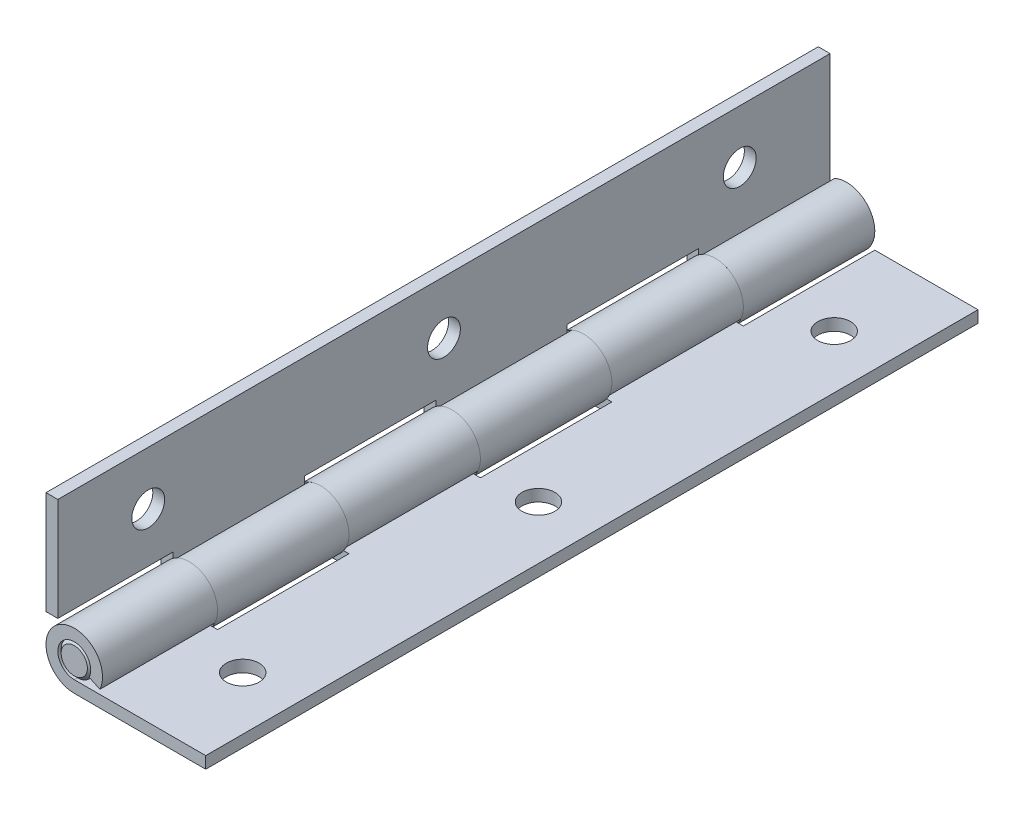
SolidWorks part; units mm, degrees
note: '?' marks a value the reader was unsure of.
material "6061-T6 (SS)"
ref_plane "Front Plane" through (0, 0, 0) normal (0, 0, 1) x (1, 0, 0)
ref_plane "Top Plane" through (0, 0, 0) normal (0, 1, 0) x (1, 0, 0)
ref_plane "Right Plane" through (0, 0, 0) normal (1, 0, 0) x (0, 0, -1)
sketch "Sketch1" plane through (0, 0, 0) normal (0, 0, 1) x (1, 0, 0)
  line L0 (4.4432, -3.175) -> (25.4, -3.175)
  line L1 (25.4, -3.175) -> (25.4, -5.461)
  line L2 (25.4, -5.461) -> (0, -5.461)
  line L3 (0, 0) -> (0, 3.175) construction
  line L4 (-3.175, 0) -> (-5.461, 0) construction
  line L5 (2.8775, -1.3418) -> (4.9493, -2.3079) construction
  line L6 (-2.8775, -1.3418) -> (-4.9493, -2.3079) construction
  circle A0 centre (0, 0) radius 3.175
  circle A1 centre (0, 0) radius 5.461
  dimension "knuckle dia" = 10.922
  dimension "leaf thickness" = 2.286
  dimension "open width" = 50.8
  dimension "D5" = 25
  dimension "D6" = 25
sketch "Sketch2" plane through (0, 0, 0) normal (0, 0, 1) x (1, 0, 0)
  line L0 (25.4, -3.175) -> (25.4, -5.461) construction
  line L1 (4.4432, -3.175) -> (25.4, -3.175) construction
  line L2 (2.8775, -1.3418) -> (4.9493, -2.3079) construction
  line L3 (25.4, -5.461) -> (0, -5.461) construction
  line L4 (25.4, -3.175) -> (25.4, -5.461)
  line L5 (0, -3.175) -> (25.4, -3.175)
  line L6 (2.8775, -1.3418) -> (4.9493, -2.3079)
  line L7 (25.4, -5.461) -> (0, -5.461)
  circle A0 centre (0, 0) radius 3.175 construction
  circle A1 centre (0, 0) radius 5.461 construction
  arc A2 (2.8775, -1.3418) -> (0, -3.175) centre (0, 0) ccw
  arc A3 (4.9493, -2.3079) -> (0, -5.461) centre (0, 0) ccw
extrude "Extrude1" add sketch "Sketch2" along normal mid plane 149.225
sketch "Sketch3" plane through (0, -3.175, 0) normal (0, 1, 0) x (1, 0, 0)
  line L1 (-5.461, 74.6125) -> (5.461, 74.6125)
  line L2 (-5.461, 74.6125) -> (-5.461, 49.2125)
  line L3 (-5.461, 49.2125) -> (5.461, 49.2125)
  line L4 (5.461, 74.6125) -> (5.461, 49.2125)
  line L6 (5.461, 74.6125) -> (-5.461, 74.6125) construction
  line L7 (5.461, -74.6125) -> (5.461, 74.6125) construction
  line L8 (-5.461, 74.6125) -> (-5.461, -74.6125) construction
  dimension "knuckle length" = 25.4
extrude "Cut-Extrude1" cut sketch "Sketch3" against normal mid plane 50.8
pattern_linear "LPattern1" count 3 spacing 50.8 along (0, 0, 1) of "Cut-Extrude1"
sketch "Sketch5" plane through (0, 0, -74.6125) normal (0, 0, -1) x (-1, 0, 0)
  line L0 (-4.4432, -3.175) -> (-25.4, -3.175) construction
  line L1 (-25.4, -5.461) -> (0, -5.461) construction
  line L2 (0, -3.175) -> (25.4, -3.175)
  line L3 (25.4, -5.461) -> (0, -5.461)
  line L4 (2.8775, -1.3418) -> (4.9493, -2.3079) construction
  line L5 (2.8775, -1.3418) -> (4.9493, -2.3079)
  line L6 (25.4, -3.175) -> (25.4, -5.461)
  line L8 (0, 0) -> (0, -5.461) construction
  circle A0 centre (0, 0) radius 5.461 construction
  arc A1 (4.9493, -2.3079) -> (0, -5.461) centre (0, 0) ccw
  circle A2 centre (0, 0) radius 3.175 construction
  arc A3 (2.8775, -1.3418) -> (0, -3.175) centre (0, 0) ccw
  dimension "D1" = 50.8
extrude "Extrude2" add sketch "Sketch5" against normal blind 25.4 separate body
pattern_linear "LPattern3" count 3 spacing 50.8 along (0, 0, 1) of bodies 104
sketch "Sketch6" plane through (0, 0, -74.6125) normal (0, 0, -1) x (-1, 0, 0)
  line L0 (0, -5.461) -> (25.4, -5.461) construction
  line L1 (25.4, -3.175) -> (5.4864, -3.175)
  line L2 (25.4, -3.175) -> (25.4, -5.461)
  line L3 (25.4, -5.461) -> (5.4864, -5.461)
  line L4 (5.4864, -3.175) -> (5.4864, -5.461)
  line L6 (25.4, -3.175) -> (0, -3.175) construction
  line L7 (5.461, 1.5054) -> (5.461, -2.5761) construction
  arc A0 (4.9493, -2.3079) -> (0, -5.461) centre (0, 0) ccw construction
  dimension "D1" = 0.0254
extrude "Extrude5" add sketch "Sketch6" against normal blind 149.225
sketch "Sketch7" plane through (0, 0, 0) normal (0, 0, 1) x (1, 0, 0)
  circle A0 centre (0, 0) radius 3.175 construction
  circle A1 centre (0, 0) radius 3.175
extrude "Extrude4" add sketch "Sketch7" along normal mid plane 149.225 separate body
chamfer "Chamfer1" distance 0.635 angle 45 2 edges at (3.175, 0, 74.6125) (3.175, 0, -74.6125)
sketch "Sketch8" plane through (0, 0, 0) normal (0, 1, 0) x (1, 0, 0)
  line L0 (25.4, 0) -> (-25.4, 0) construction
  line L1 (25.4, 0) -> (0, 0) construction
  line L2 (-25.4, -74.6125) -> (-25.4, 74.6125) construction
  line L3 (25.4, -74.6125) -> (25.4, 74.6125) construction
ref_axis "Axis1" through (-25.4, 0, 0) along (1, 0, 0)?
ref_plane "  " through (0, 0, 0) normal (0, 0.866, 0.5) x (1, 0, 0)
sketch "Sketch9" plane through (0, 0, 0) normal (0, 1, 0) x (1, 0, 0)
  line L0 (5.461, 49.2125) -> (5.461, 74.6125) construction
  point P0 (-25.4, 74.6125)
  point P1 (25.4, 74.6125)
  point P3 (-25.4, -74.6125)
  point P5 (25.4, -74.6125)
  point P7 (5.461, 49.2125)
sketch "Sketch11" plane through (0, 0, 0) normal (0, 0, 1) x (1, 0, 0)
  line L0 (-5.461, 0) -> (-5.461, -5.461)
  line L1 (-5.461, -5.461) -> (5.461, -5.461)
  line L2 (5.461, -5.461) -> (5.461, 0)
  line L3 (0, -5.461) -> (25.4, -5.461) construction
  circle A0 centre (0, 0) radius 5.461
  circle A1 centre (0, 0) radius 5.461 construction
sketch "Sketch12" plane through (0, -3.175, 0) normal (0, 1, 0) x (1, 0, 0)
  line L0 (31.5242, 0) -> (-103.7671, 0) construction
  line L1 (0, -45.7265) -> (0, 82.3405) construction
  circle A0 centre (-15.0812, 57.15) radius 3.175
  circle A1 centre (-15.0812, 0) radius 3.175
  circle A2 centre (-15.0812, -57.15) radius 3.175
  circle A3 centre (15.0812, 0) radius 3.175
  circle A4 centre (15.0812, 57.15) radius 3.175
  circle A5 centre (15.0812, -57.15) radius 3.175
  dimension "D2" = 6.35
  dimension "D1" = 30.1625
  dimension "D3" = 57.15
extrude "Cut-Extrude2" cut sketch "Sketch12" against normal through all both and the other way through all
move or copy body "Body-Move/Copy1" bodies to move or copy 311 copy no rotation origin (0, 0, 0) rotation axis (0, 0, -1) rotation angle 45
move or copy body "Body-Move/Copy2" bodies to move or copy 312 copy no rotation origin (0, 0, 0) rotation axis (0, 0, -1) rotation angle 45
equation "\"D1@LPattern1\" = \"overall length@Extrude1\"/(\"knuckle length@Sketch3\"*2)"
equation "\"D1@Sketch5\" = \"open width@Sketch1\""
equation "\"D1@LPattern3\" = \"D1@LPattern1\""
equation "\"D1@Extrude4\" = \"overall length@Extrude1\""
equation "\"D3@LPattern1\" = \"knuckle length@Sketch3\"*2"
equation "\"D3@LPattern3\" = \"D3@LPattern1\""
equation "\"D1@Chamfer1\" = \"pin diameter@Sketch1\"*.1"
equation "\"D1@Extrude2\" = \"knuckle length@Sketch3\""
equation "\"D1@Extrude5\" = \"overall length@Extrude1\""
